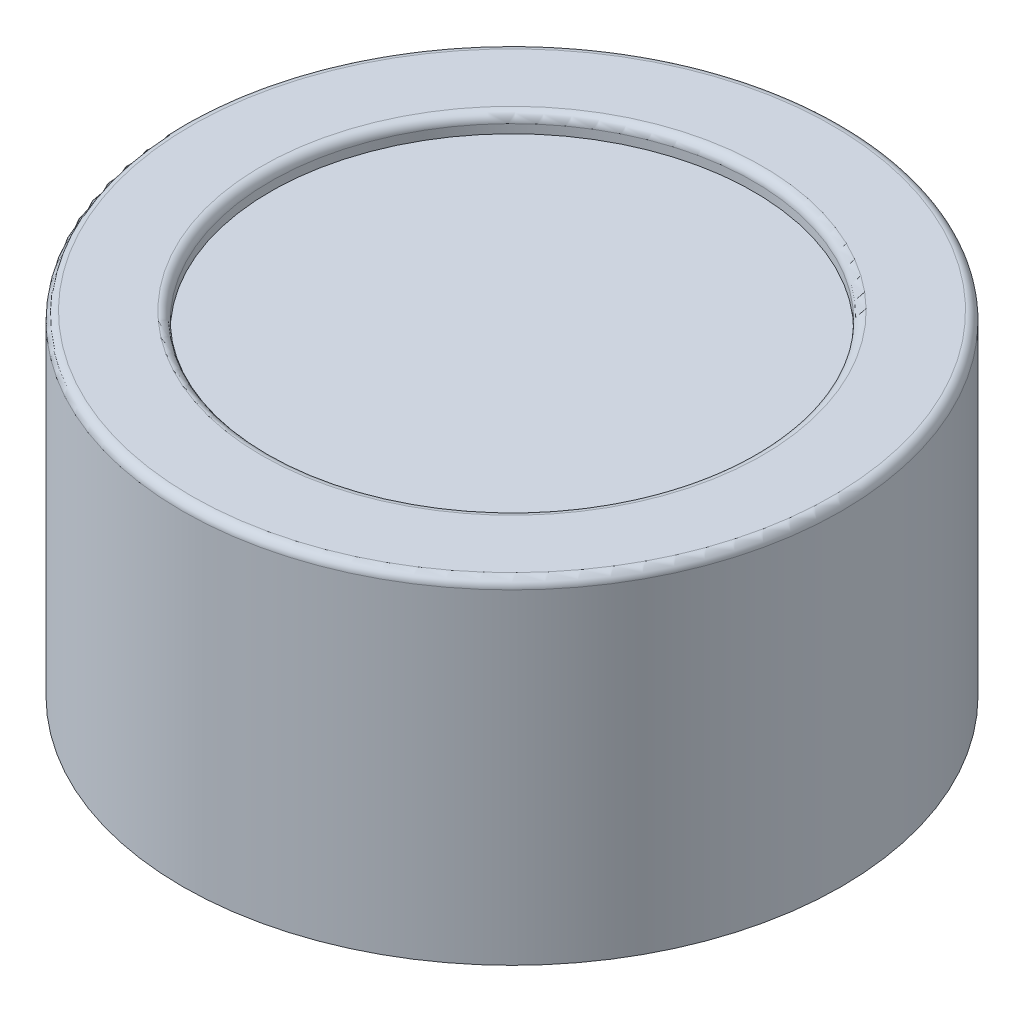
SolidWorks part; units mm, degrees
ref_plane "Спереди" through (0, 0, 0) normal (0, 0, 1) x (1, 0, 0)
ref_plane "Сверху" through (0, 0, 0) normal (0, 1, 0) x (1, 0, 0)
ref_plane "Справа" through (0, 0, 0) normal (1, 0, 0) x (0, 0, -1)
sketch "Sketch1" plane through (0, 0, 0) normal (0, 1, 0) x (1, 0, 0)
  circle A0 centre (0, 0) radius 18.75
  dimension "D1" = 37.5
extrude "Boss-Extrude1" add sketch "Sketch1" along normal blind 19
sketch "Sketch2" plane through (0, 19, 0) normal (0, 1, 0) x (1, 0, 0)
  circle A2 centre (0, 0) radius 13.75
  circle A3 centre (0, 0) radius 13.75
  dimension "D1" = 5
split line "Split Line1"
extrude "Cut-Extrude2" cut sketch "Sketch2<4>" against normal blind 1
sketch "Sketch2<4>" plane through (0, 19, 0) normal (0, 1, 0) x (1, 0, 0) same geometry as "Sketch2"
fillet "Fillet1" radius 0.5 2 edges at (0, 19, 18.75) (0, 19, 13.75)
